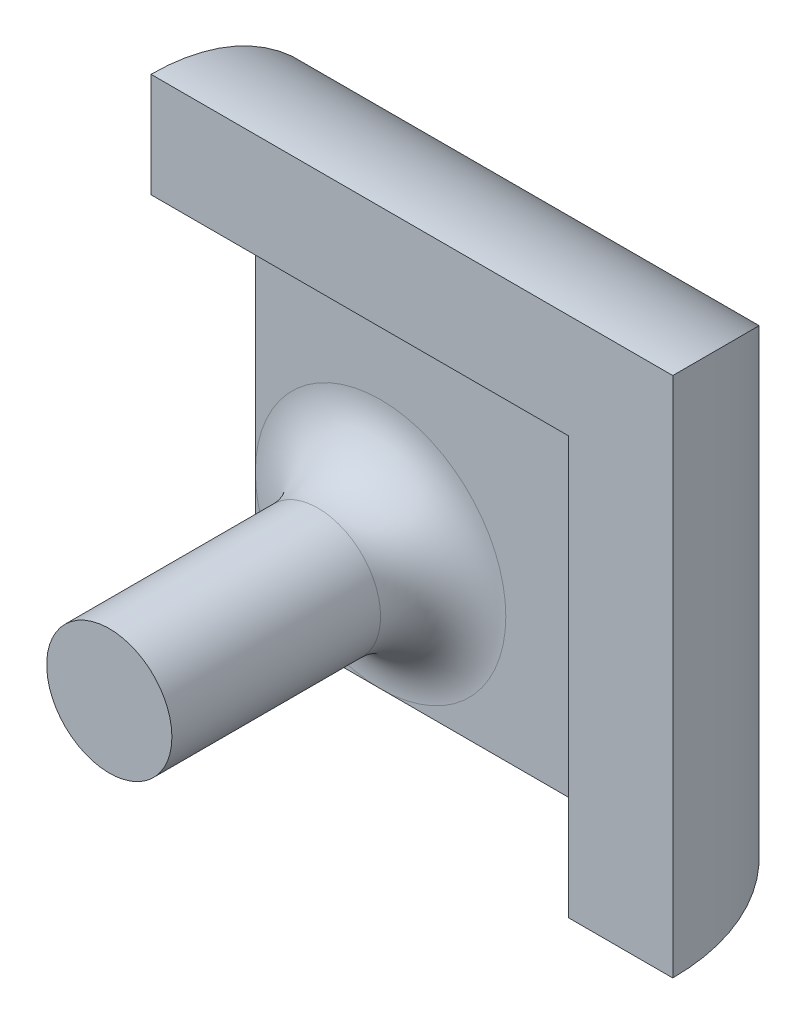
SolidWorks part; units mm, degrees
ref_plane "Alzado" through (0, 0, 0) normal (0, 0, 1) x (1, 0, 0)
ref_plane "Planta" through (0, 0, 0) normal (0, 1, 0) x (1, 0, 0)
ref_plane "Vista lateral" through (0, 0, 0) normal (1, 0, 0) x (0, 0, -1)
sketch "Croquis1" plane through (0, 0, 0) normal (0, 0, 1) x (1, 0, 0)
  line L1 (-45.1504, 20.9356) -> (-20.1504, 20.9356)
  line L2 (-45.1504, 20.9356) -> (-45.1504, -4.0644)
  line L3 (-45.1504, -4.0644) -> (-20.1504, -4.0644)
  line L4 (-20.1504, 20.9356) -> (-20.1504, -4.0644)
  dimension "D1" = 25
  dimension "D2" = 25
extrude "Saliente-Extruir1" add sketch "Croquis1" along normal blind 10
fillet "Redondeo1" radius 10 2 edges at (-20.1504, 8.4356, 0) (-32.6504, 20.9356, 0)
shell "Vaciado1" thickness 5 removed face at (-32.6504, 8.4356, 10) removed face at (-45.1504, 6.4533, 4.4822) removed face at (-34.6326, -4.0644, 4.4822)
sketch "Croquis4" plane through (0, 0, 5) normal (0, 0, 1) x (1, 0, 0)
  line L0 (-20.1504, -4.0644) -> (-20.1504, 20.9356) construction
  line L1 (-20.1504, 20.9356) -> (-45.1504, 20.9356) construction
  circle A0 centre (-39.1504, 1.9356) radius 3
  dimension "D1" = 19
  dimension "D2" = 19
extrude "Saliente-Extruir3" add sketch "Croquis4" along normal offset from surface (13 mm away) 8 up to face at (-30.1504, 10.9356, 10) offset beyond the face yes
fillet "Redondeo2" radius 3 1 edges at (-36.1504, 1.9356, 5)
